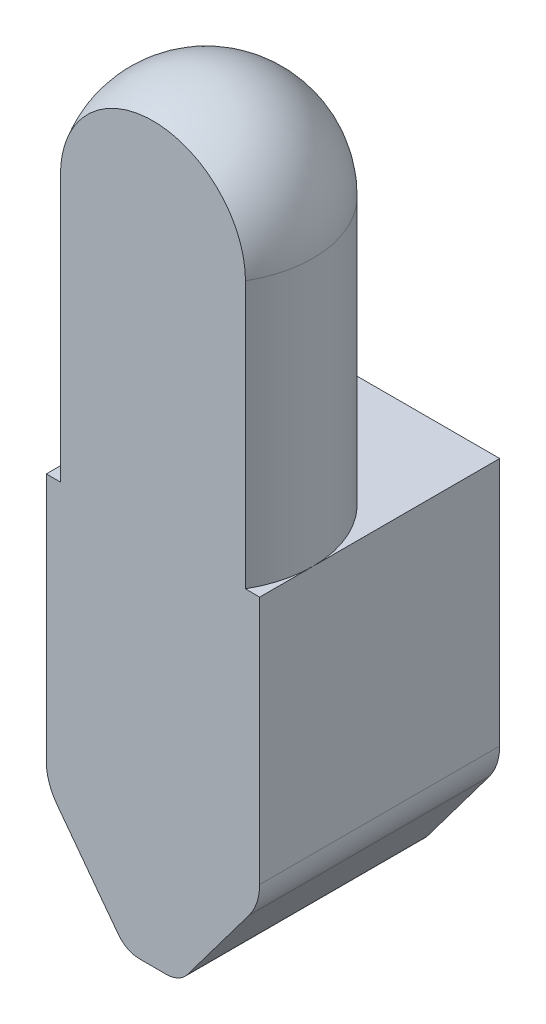
SolidWorks part; units mm, degrees
ref_plane "Спереди" through (0, 0, 0) normal (0, 0, 1) x (1, 0, 0)
ref_plane "Сверху" through (0, 0, 0) normal (0, 1, 0) x (1, 0, 0)
ref_plane "Справа" through (0, 0, 0) normal (1, 0, 0) x (0, 0, -1)
sketch "Эскиз1" plane through (0, 0, 0) normal (0, 0, 1) x (1, 0, 0)
  line L0 (0, 0) -> (0, -2) construction
  line L4 (2, 0) -> (2, 5)
  line L5 (-0.5, -2) -> (0.5, -2)
  line L6 (0.5, -2) -> (2, 0)
  line L7 (0, 0) -> (0, 5) construction
  line L8 (-2, 5) -> (2, 5)
  line L9 (-0.5, -2) -> (-2, 0)
  line L10 (-2, 0) -> (-2, 5)
  dimension "D1" = 5
  dimension "D2" = 2
  dimension "D3" = 2
  dimension "D4" = 0.5
extrude "Бобышка-Вытянуть1" add sketch "Эскиз1" against normal blind 4.5
sketch "Эскиз2" plane through (0, 5, 0) normal (0, 1, 0) x (1, 0, 0)
  line L0 (0, 0) -> (0, 1) construction
  line L1 (-1.7321, 0) -> (1.7321, 0)
  line L2 (2, 0) -> (-2, 0) construction
  arc A0 (1.7321, 0) -> (-1.7321, 0) centre (0, 1) ccw
  dimension "D1" = 1
extrude "Бобышка-Вытянуть2" add sketch "Эскиз2" along normal blind 5
sketch "Эскиз3" plane through (0, 10, 0) normal (0, 1, 0) x (1, 0, 0)
  line L0 (0, 0) -> (0, 3) construction
  line L1 (-1.7321, 0) -> (1.7321, 0) construction
  line L2 (2, 1) -> (0, 1) construction
  line L3 (-2, 1) -> (2, 1)
  arc A0 (2, 1) -> (-2, 1) centre (0, 1) ccw construction
  circle A1 centre (0, 1) radius 2
revolve "Повернуть1" add sketch "Эскиз3" angle 360 about L3 region at (0, 10, -1.8488)
sketch "Эскиз4" plane through (0, 0, 0) normal (0, 1, 0) x (1, 0, 0)
  line L1 (-2, 0) -> (2.1075, 0)
  line L2 (-2, 0) -> (-2, -2.2741)
  line L3 (-2, -2.2741) -> (2.1075, -2.2741)
  line L4 (2.1075, 0) -> (2.1075, -2.2741)
extrude "Вырез-Вытянуть1" cut sketch "Эскиз4" against normal through all both and the other way through all
fillet "Скругление1" radius 1 2 edges at (-2, 0, -2.25) (2, 0, -2.25)
fillet "Скругление2" radius 0.5 2 edges at (-0.5, -2, -2.25) (0.5, -2, -2.25)
